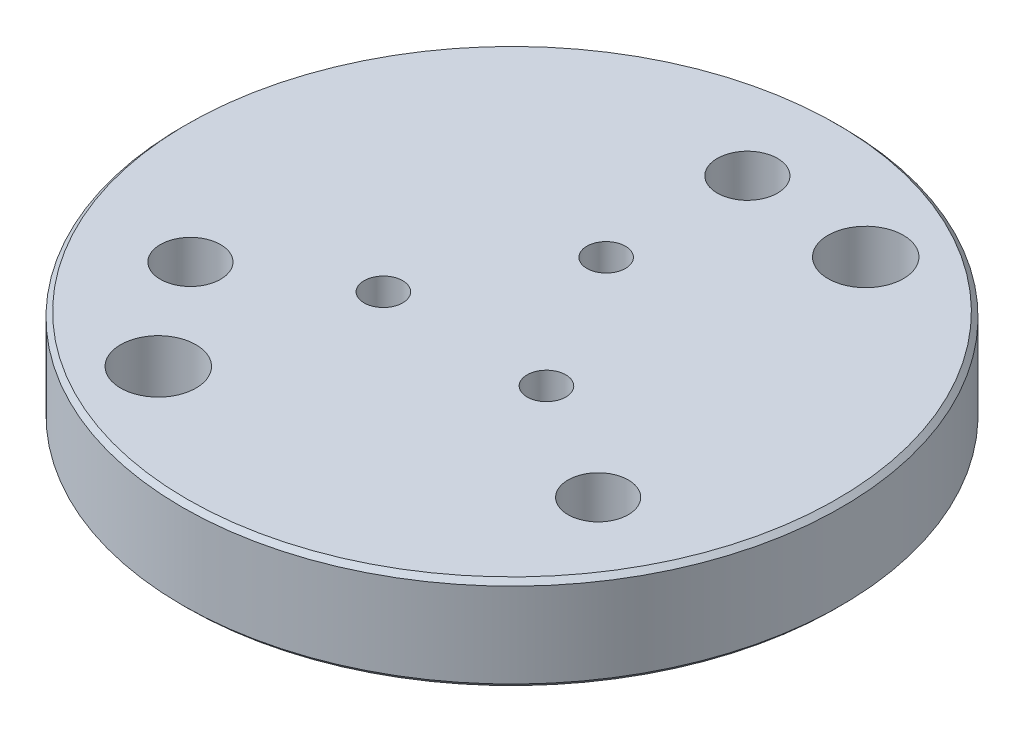
SolidWorks part; units mm, degrees
material "K110"
ref_plane "Front Plane" through (0, 0, 0) normal (0, 0, 1) x (1, 0, 0)
ref_plane "Top Plane" through (0, 0, 0) normal (0, 1, 0) x (1, 0, 0)
ref_plane "Right Plane" through (0, 0, 0) normal (1, 0, 0) x (0, 0, -1)
sketch "Sketch1" plane through (0, 0, 0) normal (0, 1, 0) x (1, 0, 0)
  circle A0 centre (0, 0) radius 35
  dimension "D1" = 70
extrude "Boss-Extrude1" add sketch "Sketch1" against normal blind 10
sketch "Sketch2" plane through (0, 0, 0) normal (0, 1, 0) x (1, 0, 0)
  circle A0 centre (8.6603, -5) radius 2.05 construction
  circle A1 centre (0, 10) radius 2.05 construction
  circle A2 centre (-8.6603, -5) radius 2.05 construction
  circle A3 centre (8.6603, -5) radius 2.05
  circle A4 centre (0, 10) radius 2.05
  circle A5 centre (-8.6603, -5) radius 2.05
  circle A6 centre (0, 0) radius 10 construction
  dimension "D1" = 20
extrude "Cut-Extrude1" cut sketch "Sketch2" against normal up to next
hole_wizard "Ø8.0mm Dowel Hole1" positions "Sketch10" profile "Sketch4" hole size "Ø8.0" standard "ISO" end condition through all
sketch "Sketch10" plane through (0, -10, 0) normal (0, -1, 0) x (-1, 0, 0)
  line L0 (0, 0) -> (-13.75, 23.8157) construction
  circle A0 centre (0, 0) radius 27.5 construction
  point P0 (-13.75, 23.8157)
  point P3 (13.75, -23.8157)
  dimension "D1" = 55
sketch "Sketch4" plane through (13.75, -10, -23.8157) normal (1, 0, 0) x (0, 0, -1)
  line L0 (0, 0) -> (0, 10)
  line L1 (0, 10) -> (4, 10)
  line L2 (4, 10) -> (4, 0)
  line L5 (4, 0) -> (0, 0)
  line L11 (0, -6.35) -> (0, 107.95) construction
  dimension "Thru Hole Dia." = 8
  dimension "Thru Hole Depth" = 10
hole_wizard "M6 Clearance Hole1" positions "Sketch11" profile "Sketch7" hole size "M6" standard "ISO" end condition through all
sketch "Sketch11" plane through (0, -10, 0) normal (0, -1, 0) x (-1, 0, 0)
  circle A1 centre (0, 0) radius 25 construction
  point P0 (-21.6506, -12.5)
  point P3 (21.6506, -12.5)
  point P7 (0, 25)
  dimension "D1" = 50
sketch "Sketch7" plane through (21.6506, -10, 12.5) normal (1, 0, 0) x (0, 0, -1)
  line L0 (0, 0) -> (0, 10)
  line L1 (0, 10) -> (3.2, 10)
  line L2 (3.2, 10) -> (3.2, 0)
  line L5 (3.2, 0) -> (0, 0)
  line L11 (0, -6.35) -> (0, 107.95) construction
  dimension "Thru Hole Dia." = 6.4
  dimension "Thru Hole Depth" = 10
chamfer "Chamfer1" distance 0.5 angle 45 2 edges at (0, 0, 35) (0, -10, 35)
